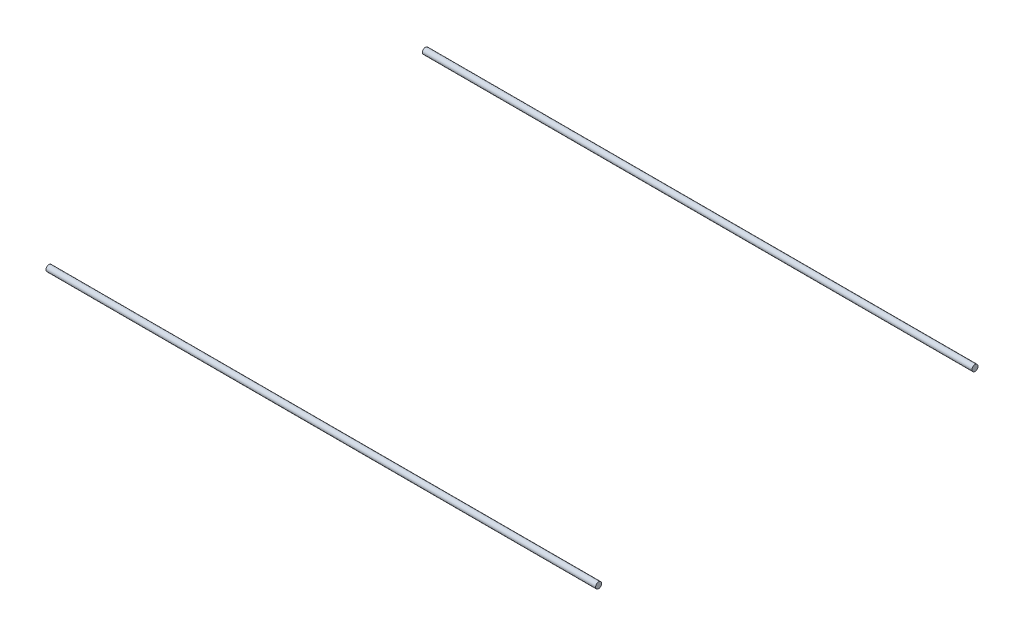
SolidWorks part; units mm, degrees
ref_plane "Front Plane" through (0, 0, 0) normal (0, 0, 1) x (1, 0, 0)
ref_plane "Top Plane" through (0, 0, 0) normal (0, 1, 0) x (1, 0, 0)
ref_plane "Right Plane" through (0, 0, 0) normal (1, 0, 0) x (0, 0, -1)
sketch "Sketch1" plane through (0, 0, 0) normal (0, 1, 0) x (1, 0, 0)
  line L1 (-350, 250) -> (350, 250)
  line L2 (-350, 250) -> (-350, -250)
  line L3 (-350, -250) -> (350, -250)
  line L4 (350, 250) -> (350, -250)
  line L5 (-350, 250) -> (350, -250) construction
  line L6 (-350, -250) -> (350, 250) construction
  point P0 (0, 0)
  dimension "D1" = 700
  dimension "D2" = 500
sketch "Sketch13" plane through (0, 0, 0) normal (0, 0, 1) x (1, 0, 0)
  line L0 (363.7, 12.7) -> (363.7, 10.5)
  line L1 (360.5, 9.5) -> (362.7, 9.5)
  line L2 (359.5, 12.7) -> (359.5, 10.5)
  line L3 (360.5, 13.7) -> (362.7, 13.7)
  line L4 (353.1359, 4.5184) -> (351.6001, 3.2806)
  line L5 (353.2806, 1.6001) -> (354.5053, 3.1547)
  line L6 (356.0045, 0.9) -> (355.4849, 0)
  line L7 (356.0045, 4.2045) -> (356.0045, 0.9)
  line L8 (350, -5.4849) -> (350.9, -6)
  line L9 (350.9, -6) -> (354.2045, -6)
  line L10 (354.2045, -6) -> (358.25, -10.05)
  line L11 (358.25, -10.05) -> (358.25, -12.6)
  line L12 (354.65, -12.8) -> (358.05, -12.8)
  line L13 (354.05, -14.3) -> (354.05, -13.4)
  line L14 (354.25, -14.5) -> (354.35, -14.5)
  line L15 (354.55, -14.8) -> (354.55, -14.7)
  line L16 (354.75, -15) -> (363, -15)
  line L17 (365, -13) -> (365, -4.75)
  line L18 (364.7, -4.55) -> (364.8, -4.55)
  line L19 (364.5, -4.35) -> (364.5, -4.25)
  line L20 (363.4, -4.05) -> (364.3, -4.05)
  line L21 (362.8, -8.05) -> (362.8, -4.65)
  line L22 (362.6, -8.25) -> (360.05, -8.25)
  line L23 (360.05, -8.25) -> (356.0045, -4.2045)
  line L24 (356.0045, -4.2045) -> (356.0045, -0.9)
  line L25 (356.0045, -0.9) -> (355.4849, 0)
  line L26 (360.05, 8.25) -> (356.0045, 4.2045)
  line L27 (362.6, 8.25) -> (360.05, 8.25)
  line L28 (362.8, 8.05) -> (362.8, 4.65)
  line L29 (363.4, 4.05) -> (364.3, 4.05)
  line L30 (364.5, 4.35) -> (364.5, 4.25)
  line L31 (364.7, 4.55) -> (364.8, 4.55)
  line L32 (365, 13) -> (365, 4.75)
  line L33 (354.75, 15) -> (363, 15)
  line L34 (354.55, 14.8) -> (354.55, 14.7)
  line L35 (354.25, 14.5) -> (354.35, 14.5)
  line L36 (354.05, 14.3) -> (354.05, 13.4)
  line L37 (354.65, 12.8) -> (358.05, 12.8)
  line L38 (358.25, 10.05) -> (358.25, 12.6)
  line L39 (354.2045, 6) -> (358.25, 10.05)
  line L40 (350.9, 6) -> (354.2045, 6)
  line L41 (350, 5.4849) -> (350.9, 6)
  line L42 (336.3, -12.7) -> (336.3, -10.5)
  line L43 (339.5, -9.5) -> (337.3, -9.5)
  line L44 (340.5, -12.7) -> (340.5, -10.5)
  line L45 (339.5, -13.7) -> (337.3, -13.7)
  line L46 (346.8641, -4.5184) -> (348.3999, -3.2806)
  line L47 (346.7194, -1.6001) -> (345.4947, -3.1547)
  line L48 (350, 5.4849) -> (349.1, 6)
  line L49 (349.1, 6) -> (345.7955, 6)
  line L50 (345.7955, 6) -> (341.75, 10.05)
  line L51 (341.75, 10.05) -> (341.75, 12.6)
  line L52 (345.35, 12.8) -> (341.95, 12.8)
  line L53 (345.95, 14.3) -> (345.95, 13.4)
  line L54 (345.75, 14.5) -> (345.65, 14.5)
  line L55 (345.45, 14.8) -> (345.45, 14.7)
  line L56 (345.25, 15) -> (337, 15)
  line L57 (335, 13) -> (335, 4.75)
  line L58 (335.3, 4.55) -> (335.2, 4.55)
  line L59 (335.5, 4.35) -> (335.5, 4.25)
  line L60 (336.6, 4.05) -> (335.7, 4.05)
  line L61 (337.2, 8.05) -> (337.2, 4.65)
  line L62 (337.4, 8.25) -> (339.95, 8.25)
  line L63 (339.95, 8.25) -> (343.9955, 4.2045)
  line L64 (343.9955, -0.9) -> (344.5151, 0)
  line L65 (343.9955, -4.2045) -> (343.9955, -0.9)
  line L66 (339.95, -8.25) -> (343.9955, -4.2045)
  line L67 (337.4, -8.25) -> (339.95, -8.25)
  line L68 (337.2, -8.05) -> (337.2, -4.65)
  line L69 (336.6, -4.05) -> (335.7, -4.05)
  line L70 (335.5, -4.35) -> (335.5, -4.25)
  line L71 (335.3, -4.55) -> (335.2, -4.55)
  line L72 (335, -13) -> (335, -4.75)
  line L73 (345.25, -15) -> (337, -15)
  line L74 (345.45, -14.8) -> (345.45, -14.7)
  line L75 (345.75, -14.5) -> (345.65, -14.5)
  line L76 (345.95, -14.3) -> (345.95, -13.4)
  line L77 (353.2806, -1.6001) -> (354.5053, -3.1547)
  line L78 (353.1359, -4.5184) -> (351.6001, -3.2806)
  line L79 (345.35, -12.8) -> (341.95, -12.8)
  line L80 (341.75, -10.05) -> (341.75, -12.6)
  line L81 (345.7955, -6) -> (341.75, -10.05)
  line L82 (349.1, -6) -> (345.7955, -6)
  line L83 (350, -5.4849) -> (349.1, -6)
  line L84 (360.5, -13.7) -> (362.7, -13.7)
  line L85 (359.5, -12.7) -> (359.5, -10.5)
  line L86 (360.5, -9.5) -> (362.7, -9.5)
  line L87 (363.7, -12.7) -> (363.7, -10.5)
  line L88 (343.9955, 4.2045) -> (343.9955, 0.9)
  line L89 (343.9955, 0.9) -> (344.5151, 0)
  line L90 (346.7194, 1.6001) -> (345.4947, 3.1547)
  line L91 (346.8641, 4.5184) -> (348.3999, 3.2806)
  line L92 (339.5, 13.7) -> (337.3, 13.7)
  line L93 (340.5, 12.7) -> (340.5, 10.5)
  line L94 (339.5, 9.5) -> (337.3, 9.5)
  line L95 (336.3, 12.7) -> (336.3, 10.5)
  line L96 (335, 0) -> (365, 0) construction
  line L97 (350, 15) -> (350, -15) construction
  line L98 (-337.4, 8.25) -> (-339.95, 8.25)
  line L99 (-354.2045, 6) -> (-358.25, 10.05)
  line L100 (-360.05, -8.25) -> (-356.0045, -4.2045)
  line L101 (-336.3, -12.7) -> (-336.3, -10.5)
  line L102 (-346.7194, 1.6001) -> (-345.4947, 3.1547)
  line L103 (-337.2, 8.05) -> (-337.2, 4.65)
  line L104 (-335.5, 4.35) -> (-335.5, 4.25)
  line L105 (-350, 5.4849) -> (-350.9, 6)
  line L106 (-362.8, 8.05) -> (-362.8, 4.65)
  line L107 (-350.9, -6) -> (-354.2045, -6)
  line L108 (-343.9955, 0.9) -> (-344.5151, 0)
  line L109 (-343.9955, 4.2045) -> (-343.9955, 0.9)
  line L110 (-339.95, -8.25) -> (-343.9955, -4.2045)
  line L111 (-345.75, 14.5) -> (-345.65, 14.5)
  line L112 (-354.05, 14.3) -> (-354.05, 13.4)
  line L113 (-350, -5.4849) -> (-350.9, -6)
  line L114 (-356.0045, 4.2045) -> (-356.0045, 0.9)
  line L115 (-336.3, 12.7) -> (-336.3, 10.5)
  line L116 (-349.1, -6) -> (-345.7955, -6)
  line L117 (-345.45, 14.8) -> (-345.45, 14.7)
  line L118 (-359.5, -12.7) -> (-359.5, -10.5)
  line L119 (-362.8, -8.05) -> (-362.8, -4.65)
  line L120 (-354.05, -14.3) -> (-354.05, -13.4)
  line L121 (-336.6, -4.05) -> (-335.7, -4.05)
  line L122 (-360.5, -9.5) -> (-362.7, -9.5)
  line L123 (-362.6, 8.25) -> (-360.05, 8.25)
  line L124 (-346.7194, -1.6001) -> (-345.4947, -3.1547)
  line L125 (-363.7, 12.7) -> (-363.7, 10.5)
  line L126 (-345.95, -14.3) -> (-345.95, -13.4)
  line L127 (-358.25, 10.05) -> (-358.25, 12.6)
  line L128 (-354.75, 15) -> (-363, 15)
  line L129 (-364.7, -4.55) -> (-364.8, -4.55)
  line L130 (-356.0045, 0.9) -> (-355.4849, 0)
  line L131 (-350, 15) -> (-350, -15) construction
  line L132 (-341.75, -10.05) -> (-341.75, -12.6)
  line L133 (-345.45, -14.8) -> (-345.45, -14.7)
  line L134 (-335.3, 4.55) -> (-335.2, 4.55)
  line L135 (-345.25, 15) -> (-337, 15)
  line L136 (-364.7, 4.55) -> (-364.8, 4.55)
  line L137 (-339.5, -13.7) -> (-337.3, -13.7)
  line L138 (-360.5, 9.5) -> (-362.7, 9.5)
  line L139 (-339.5, 9.5) -> (-337.3, 9.5)
  line L140 (-345.25, -15) -> (-337, -15)
  line L141 (-343.9955, -4.2045) -> (-343.9955, -0.9)
  line L142 (-341.75, 10.05) -> (-341.75, 12.6)
  line L143 (-354.25, 14.5) -> (-354.35, 14.5)
  line L144 (-360.05, 8.25) -> (-356.0045, 4.2045)
  line L145 (-346.8641, 4.5184) -> (-348.3999, 3.2806)
  line L146 (-345.35, -12.8) -> (-341.95, -12.8)
  line L147 (-345.95, 14.3) -> (-345.95, 13.4)
  line L148 (-360.5, -13.7) -> (-362.7, -13.7)
  line L149 (-364.5, -4.35) -> (-364.5, -4.25)
  line L150 (-346.8641, -4.5184) -> (-348.3999, -3.2806)
  line L151 (-337.4, -8.25) -> (-339.95, -8.25)
  line L152 (-353.1359, -4.5184) -> (-351.6001, -3.2806)
  line L153 (-362.6, -8.25) -> (-360.05, -8.25)
  line L154 (-354.65, -12.8) -> (-358.05, -12.8)
  line L155 (-353.1359, 4.5184) -> (-351.6001, 3.2806)
  line L156 (-345.7955, -6) -> (-341.75, -10.05)
  line L157 (-345.7955, 6) -> (-341.75, 10.05)
  line L158 (-354.65, 12.8) -> (-358.05, 12.8)
  line L159 (-354.55, 14.8) -> (-354.55, 14.7)
  line L160 (-365, -13) -> (-365, -4.75)
  line L161 (-353.2806, 1.6001) -> (-354.5053, 3.1547)
  line L162 (-365, 0) -> (-335, 0) construction
  line L163 (-345.75, -14.5) -> (-345.65, -14.5)
  line L164 (-335, -13) -> (-335, -4.75)
  line L165 (-345.35, 12.8) -> (-341.95, 12.8)
  line L166 (-364.5, 4.35) -> (-364.5, 4.25)
  line L167 (-354.75, -15) -> (-363, -15)
  line L168 (-340.5, -12.7) -> (-340.5, -10.5)
  line L169 (-335.3, -4.55) -> (-335.2, -4.55)
  line L170 (-343.9955, -0.9) -> (-344.5151, 0)
  line L171 (-350.9, 6) -> (-354.2045, 6)
  line L172 (-356.0045, -0.9) -> (-355.4849, 0)
  line L173 (-339.5, -9.5) -> (-337.3, -9.5)
  line L174 (-340.5, 12.7) -> (-340.5, 10.5)
  line L175 (-339.95, 8.25) -> (-343.9955, 4.2045)
  line L176 (-335, 13) -> (-335, 4.75)
  line L177 (-353.2806, -1.6001) -> (-354.5053, -3.1547)
  line L178 (-365, 13) -> (-365, 4.75)
  line L179 (-358.25, -10.05) -> (-358.25, -12.6)
  line L180 (-360.5, 13.7) -> (-362.7, 13.7)
  line L181 (-339.5, 13.7) -> (-337.3, 13.7)
  line L182 (-337.2, -8.05) -> (-337.2, -4.65)
  line L183 (-350, 5.4849) -> (-349.1, 6)
  line L184 (-363.4, -4.05) -> (-364.3, -4.05)
  line L185 (-354.2045, -6) -> (-358.25, -10.05)
  line L186 (-359.5, 12.7) -> (-359.5, 10.5)
  line L187 (-350, -5.4849) -> (-349.1, -6)
  line L188 (-336.6, 4.05) -> (-335.7, 4.05)
  line L189 (-349.1, 6) -> (-345.7955, 6)
  line L190 (-356.0045, -4.2045) -> (-356.0045, -0.9)
  line L191 (-354.55, -14.8) -> (-354.55, -14.7)
  line L192 (-335.5, -4.35) -> (-335.5, -4.25)
  line L193 (-363.7, -12.7) -> (-363.7, -10.5)
  line L194 (-363.4, 4.05) -> (-364.3, 4.05)
  line L195 (-354.25, -14.5) -> (-354.35, -14.5)
  arc A0 (363.7, 12.7) -> (362.7, 13.7) centre (362.7, 12.7) ccw
  arc A1 (362.7, 9.5) -> (363.7, 10.5) centre (362.7, 10.5) ccw
  arc A2 (359.5, 10.5) -> (360.5, 9.5) centre (360.5, 10.5) ccw
  arc A3 (360.5, 13.7) -> (359.5, 12.7) centre (360.5, 12.7) ccw
  arc A4 (351.6001, 3.2806) -> (348.3999, 3.2806) centre (350, 0) ccw
  arc A5 (358.25, -12.6) -> (358.05, -12.8) centre (358.05, -12.6) cw
  arc A6 (354.65, -12.8) -> (354.05, -13.4) centre (354.65, -13.4) ccw
  arc A7 (354.05, -14.3) -> (354.25, -14.5) centre (354.25, -14.3) ccw
  arc A8 (354.35, -14.5) -> (354.55, -14.7) centre (354.35, -14.7) cw
  arc A9 (354.55, -14.8) -> (354.75, -15) centre (354.75, -14.8) ccw
  arc A10 (363, -15) -> (365, -13) centre (363, -13) ccw
  arc A11 (365, -4.75) -> (364.8, -4.55) centre (364.8, -4.75) ccw
  arc A12 (364.7, -4.55) -> (364.5, -4.35) centre (364.7, -4.35) cw
  arc A13 (364.5, -4.25) -> (364.3, -4.05) centre (364.3, -4.25) ccw
  arc A14 (363.4, -4.05) -> (362.8, -4.65) centre (363.4, -4.65) ccw
  arc A15 (362.8, -8.05) -> (362.6, -8.25) centre (362.6, -8.05) cw
  arc A16 (354.5053, 3.1547) -> (353.1359, 4.5184) centre (350, 0) ccw
  arc A17 (362.8, 8.05) -> (362.6, 8.25) centre (362.6, 8.05) ccw
  arc A18 (363.4, 4.05) -> (362.8, 4.65) centre (363.4, 4.65) cw
  arc A19 (364.5, 4.25) -> (364.3, 4.05) centre (364.3, 4.25) cw
  arc A20 (364.7, 4.55) -> (364.5, 4.35) centre (364.7, 4.35) ccw
  arc A21 (365, 4.75) -> (364.8, 4.55) centre (364.8, 4.75) cw
  arc A22 (363, 15) -> (365, 13) centre (363, 13) cw
  arc A23 (354.55, 14.8) -> (354.75, 15) centre (354.75, 14.8) cw
  arc A24 (354.35, 14.5) -> (354.55, 14.7) centre (354.35, 14.7) ccw
  arc A25 (354.05, 14.3) -> (354.25, 14.5) centre (354.25, 14.3) cw
  arc A26 (354.65, 12.8) -> (354.05, 13.4) centre (354.65, 13.4) cw
  arc A27 (358.25, 12.6) -> (358.05, 12.8) centre (358.05, 12.6) ccw
  arc A28 (336.3, -12.7) -> (337.3, -13.7) centre (337.3, -12.7) ccw
  arc A29 (337.3, -9.5) -> (336.3, -10.5) centre (337.3, -10.5) ccw
  arc A30 (340.5, -10.5) -> (339.5, -9.5) centre (339.5, -10.5) ccw
  arc A31 (339.5, -13.7) -> (340.5, -12.7) centre (339.5, -12.7) ccw
  arc A32 (345.4947, -3.1547) -> (346.8641, -4.5184) centre (350, 0) ccw
  arc A33 (346.7194, 1.6001) -> (346.7194, -1.6001) centre (350, 0) ccw
  arc A34 (341.75, 12.6) -> (341.95, 12.8) centre (341.95, 12.6) cw
  arc A35 (345.35, 12.8) -> (345.95, 13.4) centre (345.35, 13.4) ccw
  arc A36 (345.95, 14.3) -> (345.75, 14.5) centre (345.75, 14.3) ccw
  arc A37 (345.65, 14.5) -> (345.45, 14.7) centre (345.65, 14.7) cw
  arc A38 (345.45, 14.8) -> (345.25, 15) centre (345.25, 14.8) ccw
  arc A39 (337, 15) -> (335, 13) centre (337, 13) ccw
  arc A40 (335, 4.75) -> (335.2, 4.55) centre (335.2, 4.75) ccw
  arc A41 (335.3, 4.55) -> (335.5, 4.35) centre (335.3, 4.35) cw
  arc A42 (335.5, 4.25) -> (335.7, 4.05) centre (335.7, 4.25) ccw
  arc A43 (336.6, 4.05) -> (337.2, 4.65) centre (336.6, 4.65) ccw
  arc A44 (337.2, 8.05) -> (337.4, 8.25) centre (337.4, 8.05) cw
  arc A45 (345.4947, 3.1547) -> (346.8641, 4.5184) centre (350, 0) cw
  arc A46 (337.2, -8.05) -> (337.4, -8.25) centre (337.4, -8.05) ccw
  arc A47 (336.6, -4.05) -> (337.2, -4.65) centre (336.6, -4.65) cw
  arc A48 (335.5, -4.25) -> (335.7, -4.05) centre (335.7, -4.25) cw
  arc A49 (353.2806, 1.6001) -> (353.2806, -1.6001) centre (350, 0) cw
  arc A50 (354.5053, -3.1547) -> (353.1359, -4.5184) centre (350, 0) cw
  arc A51 (351.6001, -3.2806) -> (348.3999, -3.2806) centre (350, 0) cw
  arc A52 (335.3, -4.55) -> (335.5, -4.35) centre (335.3, -4.35) ccw
  arc A53 (335, -4.75) -> (335.2, -4.55) centre (335.2, -4.75) cw
  arc A54 (337, -15) -> (335, -13) centre (337, -13) cw
  arc A55 (345.45, -14.8) -> (345.25, -15) centre (345.25, -14.8) cw
  arc A56 (360.5, -13.7) -> (359.5, -12.7) centre (360.5, -12.7) cw
  arc A57 (359.5, -10.5) -> (360.5, -9.5) centre (360.5, -10.5) cw
  arc A58 (362.7, -9.5) -> (363.7, -10.5) centre (362.7, -10.5) cw
  arc A59 (363.7, -12.7) -> (362.7, -13.7) centre (362.7, -12.7) cw
  arc A60 (345.65, -14.5) -> (345.45, -14.7) centre (345.65, -14.7) ccw
  arc A61 (345.95, -14.3) -> (345.75, -14.5) centre (345.75, -14.3) cw
  arc A62 (345.35, -12.8) -> (345.95, -13.4) centre (345.35, -13.4) cw
  arc A63 (341.75, -12.6) -> (341.95, -12.8) centre (341.95, -12.6) ccw
  arc A64 (339.5, 13.7) -> (340.5, 12.7) centre (339.5, 12.7) cw
  arc A65 (340.5, 10.5) -> (339.5, 9.5) centre (339.5, 10.5) cw
  arc A66 (337.3, 9.5) -> (336.3, 10.5) centre (337.3, 10.5) cw
  arc A67 (336.3, 12.7) -> (337.3, 13.7) centre (337.3, 12.7) cw
  arc A68 (-335.5, -4.25) -> (-335.7, -4.05) centre (-335.7, -4.25) ccw
  arc A69 (-335, 4.75) -> (-335.2, 4.55) centre (-335.2, 4.75) cw
  arc A70 (-360.5, -13.7) -> (-359.5, -12.7) centre (-360.5, -12.7) ccw
  arc A71 (-354.65, -12.8) -> (-354.05, -13.4) centre (-354.65, -13.4) cw
  arc A72 (-360.5, 13.7) -> (-359.5, 12.7) centre (-360.5, 12.7) cw
  arc A73 (-340.5, 10.5) -> (-339.5, 9.5) centre (-339.5, 10.5) ccw
  arc A74 (-337, 15) -> (-335, 13) centre (-337, 13) cw
  arc A75 (-345.95, 14.3) -> (-345.75, 14.5) centre (-345.75, 14.3) cw
  arc A76 (-345.35, 12.8) -> (-345.95, 13.4) centre (-345.35, 13.4) cw
  arc A77 (-339.5, -13.7) -> (-340.5, -12.7) centre (-339.5, -12.7) cw
  arc A78 (-362.7, 9.5) -> (-363.7, 10.5) centre (-362.7, 10.5) cw
  arc A79 (-345.65, -14.5) -> (-345.45, -14.7) centre (-345.65, -14.7) cw
  arc A80 (-354.5053, 3.1547) -> (-353.1359, 4.5184) centre (-350, 0) cw
  arc A81 (-363, -15) -> (-365, -13) centre (-363, -13) cw
  arc A82 (-341.75, -12.6) -> (-341.95, -12.8) centre (-341.95, -12.6) cw
  arc A83 (-345.35, -12.8) -> (-345.95, -13.4) centre (-345.35, -13.4) ccw
  arc A84 (-354.35, 14.5) -> (-354.55, 14.7) centre (-354.35, 14.7) cw
  arc A85 (-363, 15) -> (-365, 13) centre (-363, 13) ccw
  arc A86 (-358.25, -12.6) -> (-358.05, -12.8) centre (-358.05, -12.6) ccw
  arc A87 (-337.3, 9.5) -> (-336.3, 10.5) centre (-337.3, 10.5) ccw
  arc A88 (-341.75, 12.6) -> (-341.95, 12.8) centre (-341.95, 12.6) ccw
  arc A89 (-364.5, 4.25) -> (-364.3, 4.05) centre (-364.3, 4.25) ccw
  arc A90 (-359.5, 10.5) -> (-360.5, 9.5) centre (-360.5, 10.5) cw
  arc A91 (-363.4, 4.05) -> (-362.8, 4.65) centre (-363.4, 4.65) ccw
  arc A92 (-362.8, 8.05) -> (-362.6, 8.25) centre (-362.6, 8.05) cw
  arc A93 (-363.7, 12.7) -> (-362.7, 13.7) centre (-362.7, 12.7) cw
  arc A94 (-335.3, -4.55) -> (-335.5, -4.35) centre (-335.3, -4.35) cw
  arc A95 (-359.5, -10.5) -> (-360.5, -9.5) centre (-360.5, -10.5) ccw
  arc A96 (-364.7, -4.55) -> (-364.5, -4.35) centre (-364.7, -4.35) ccw
  arc A97 (-337.3, -9.5) -> (-336.3, -10.5) centre (-337.3, -10.5) cw
  arc A98 (-345.45, -14.8) -> (-345.25, -15) centre (-345.25, -14.8) ccw
  arc A99 (-337, -15) -> (-335, -13) centre (-337, -13) ccw
  arc A100 (-362.8, -8.05) -> (-362.6, -8.25) centre (-362.6, -8.05) ccw
  arc A101 (-345.4947, -3.1547) -> (-346.8641, -4.5184) centre (-350, 0) cw
  arc A102 (-337.2, -8.05) -> (-337.4, -8.25) centre (-337.4, -8.05) cw
  arc A103 (-336.6, 4.05) -> (-337.2, 4.65) centre (-336.6, 4.65) cw
  arc A104 (-345.45, 14.8) -> (-345.25, 15) centre (-345.25, 14.8) cw
  arc A105 (-363.4, -4.05) -> (-362.8, -4.65) centre (-363.4, -4.65) cw
  arc A106 (-339.5, 13.7) -> (-340.5, 12.7) centre (-339.5, 12.7) ccw
  arc A107 (-354.5053, -3.1547) -> (-353.1359, -4.5184) centre (-350, 0) ccw
  arc A108 (-364.5, -4.25) -> (-364.3, -4.05) centre (-364.3, -4.25) cw
  arc A109 (-354.35, -14.5) -> (-354.55, -14.7) centre (-354.35, -14.7) ccw
  arc A110 (-363.7, -12.7) -> (-362.7, -13.7) centre (-362.7, -12.7) ccw
  arc A111 (-346.7194, 1.6001) -> (-346.7194, -1.6001) centre (-350, 0) cw
  arc A112 (-336.3, 12.7) -> (-337.3, 13.7) centre (-337.3, 12.7) ccw
  arc A113 (-345.95, -14.3) -> (-345.75, -14.5) centre (-345.75, -14.3) ccw
  arc A114 (-358.25, 12.6) -> (-358.05, 12.8) centre (-358.05, 12.6) cw
  arc A115 (-354.55, 14.8) -> (-354.75, 15) centre (-354.75, 14.8) ccw
  arc A116 (-354.05, -14.3) -> (-354.25, -14.5) centre (-354.25, -14.3) cw
  arc A117 (-337.2, 8.05) -> (-337.4, 8.25) centre (-337.4, 8.05) ccw
  arc A118 (-335.3, 4.55) -> (-335.5, 4.35) centre (-335.3, 4.35) ccw
  arc A119 (-354.65, 12.8) -> (-354.05, 13.4) centre (-354.65, 13.4) ccw
  arc A120 (-354.55, -14.8) -> (-354.75, -15) centre (-354.75, -14.8) cw
  arc A121 (-340.5, -10.5) -> (-339.5, -9.5) centre (-339.5, -10.5) cw
  arc A122 (-335.5, 4.25) -> (-335.7, 4.05) centre (-335.7, 4.25) cw
  arc A123 (-362.7, -9.5) -> (-363.7, -10.5) centre (-362.7, -10.5) ccw
  arc A124 (-348.3999, -3.2806) -> (-351.6001, -3.2806) centre (-350, 0) cw
  arc A125 (-348.3999, 3.2806) -> (-351.6001, 3.2806) centre (-350, 0) ccw
  arc A126 (-365, 4.75) -> (-364.8, 4.55) centre (-364.8, 4.75) ccw
  arc A127 (-365, -4.75) -> (-364.8, -4.55) centre (-364.8, -4.75) cw
  arc A128 (-336.6, -4.05) -> (-337.2, -4.65) centre (-336.6, -4.65) ccw
  arc A129 (-345.65, 14.5) -> (-345.45, 14.7) centre (-345.65, 14.7) ccw
  arc A130 (-353.2806, 1.6001) -> (-353.2806, -1.6001) centre (-350, 0) ccw
  arc A131 (-335, -4.75) -> (-335.2, -4.55) centre (-335.2, -4.75) ccw
  arc A132 (-345.4947, 3.1547) -> (-346.8641, 4.5184) centre (-350, 0) ccw
  arc A133 (-354.05, 14.3) -> (-354.25, 14.5) centre (-354.25, 14.3) ccw
  arc A134 (-364.7, 4.55) -> (-364.5, 4.35) centre (-364.7, 4.35) cw
  arc A135 (-336.3, -12.7) -> (-337.3, -13.7) centre (-337.3, -12.7) cw
  point P81 (365, 15)
  point P82 (350, 15)
  point P203 (350, -15)
  point P204 (365, -15)
  point P206 (350, 0)
  point P207 (365, 0)
  point P219 (335, 0)
  point P220 (335, -15)
  point P221 (335, 15)
  point P319 (-335, 15)
  point P320 (-350, 15)
  point P441 (-350, -15)
  point P442 (-335, -15)
  point P444 (-350, 0)
  point P445 (-335, 0)
  point P457 (-365, 0)
  point P458 (-365, -15)
  point P459 (-365, 15)
extrude "Boss-Extrude1" add sketch "Sketch13" along normal mid plane 530
sketch "Sketch14" plane through (0, 0, 0) normal (1, 0, 0) x (0, 0, -1)
  line L194 (-246.8641, 4.5184) -> (-248.3999, 3.2806)
  line L195 (-235.3, 4.55) -> (-235.2, 4.55)
  line L196 (-260.5, -9.5) -> (-262.7, -9.5)
  line L197 (-258.25, 10.05) -> (-258.25, 12.6)
  line L198 (-264.5, -4.35) -> (-264.5, -4.25)
  line L199 (-259.5, 12.7) -> (-259.5, 10.5)
  line L200 (-250, -5.4849) -> (-249.1, -6)
  line L201 (-237.4, -8.25) -> (-239.95, -8.25)
  line L202 (-254.55, 14.8) -> (-254.55, 14.7)
  line L203 (-262.8, 8.05) -> (-262.8, 4.65)
  line L204 (-262.6, -8.25) -> (-260.05, -8.25)
  line L205 (-250, 15) -> (-250, -15) construction
  line L206 (-236.3, 12.7) -> (-236.3, 10.5)
  line L207 (-239.95, 8.25) -> (-243.9955, 4.2045)
  line L208 (-241.75, 10.05) -> (-241.75, 12.6)
  line L209 (-253.1359, -4.5184) -> (-251.6001, -3.2806)
  line L210 (-254.25, -14.5) -> (-254.35, -14.5)
  line L211 (-256.0045, 0.9) -> (-255.4849, 0)
  line L212 (-243.9955, -4.2045) -> (-243.9955, -0.9)
  line L213 (-245.7955, 6) -> (-241.75, 10.05)
  line L214 (-253.2806, -1.6001) -> (-254.5053, -3.1547)
  line L215 (-254.55, -14.8) -> (-254.55, -14.7)
  line L216 (-250.9, -6) -> (-254.2045, -6)
  line L217 (-245.35, -12.8) -> (-241.95, -12.8)
  line L218 (-243.9955, -0.9) -> (-244.5151, 0)
  line L219 (-249.1, 6) -> (-245.7955, 6)
  line L220 (-254.05, -14.3) -> (-254.05, -13.4)
  line L221 (-250, -5.4849) -> (-250.9, -6)
  line L222 (-265, 0) -> (-235, 0) construction
  line L223 (-243.9955, 0.9) -> (-244.5151, 0)
  line L224 (-245.75, -14.5) -> (-245.65, -14.5)
  line L225 (-235.5, -4.35) -> (-235.5, -4.25)
  line L226 (-263.7, -12.7) -> (-263.7, -10.5)
  line L227 (-250.9, 6) -> (-254.2045, 6)
  line L228 (-246.8641, -4.5184) -> (-248.3999, -3.2806)
  line L229 (-260.5, 9.5) -> (-262.7, 9.5)
  line L230 (-245.45, -14.8) -> (-245.45, -14.7)
  line L231 (-235.5, 4.35) -> (-235.5, 4.25)
  line L232 (-260.5, -13.7) -> (-262.7, -13.7)
  line L233 (-254.2045, 6) -> (-258.25, 10.05)
  line L234 (-265, -13) -> (-265, -4.75)
  line L235 (-239.95, -8.25) -> (-243.9955, -4.2045)
  line L236 (-259.5, -12.7) -> (-259.5, -10.5)
  line L237 (-262.6, 8.25) -> (-260.05, 8.25)
  line L238 (-246.7194, -1.6001) -> (-245.4947, -3.1547)
  line L239 (-253.2806, 1.6001) -> (-254.5053, 3.1547)
  line L240 (-245.95, -14.3) -> (-245.95, -13.4)
  line L241 (-237.4, 8.25) -> (-239.95, 8.25)
  line L242 (-254.65, 12.8) -> (-258.05, 12.8)
  line L243 (-264.7, 4.55) -> (-264.8, 4.55)
  line L244 (-254.65, -12.8) -> (-258.05, -12.8)
  line L245 (-239.5, -9.5) -> (-237.3, -9.5)
  line L246 (-243.9955, 4.2045) -> (-243.9955, 0.9)
  line L247 (-235, -13) -> (-235, -4.75)
  line L248 (-236.6, -4.05) -> (-235.7, -4.05)
  line L249 (-250, 5.4849) -> (-249.1, 6)
  line L250 (-239.5, -13.7) -> (-237.3, -13.7)
  line L251 (-240.5, -12.7) -> (-240.5, -10.5)
  line L252 (-245.7955, -6) -> (-241.75, -10.05)
  line L253 (-237.2, 8.05) -> (-237.2, 4.65)
  line L254 (-254.25, 14.5) -> (-254.35, 14.5)
  line L255 (-260.05, -8.25) -> (-256.0045, -4.2045)
  line L256 (-258.25, -10.05) -> (-258.25, -12.6)
  line L257 (-236.3, -12.7) -> (-236.3, -10.5)
  line L258 (-240.5, 12.7) -> (-240.5, 10.5)
  line L259 (-235, 13) -> (-235, 4.75)
  line L260 (-263.4, 4.05) -> (-264.3, 4.05)
  line L261 (-260.05, 8.25) -> (-256.0045, 4.2045)
  line L262 (-254.75, -15) -> (-263, -15)
  line L263 (-239.5, 9.5) -> (-237.3, 9.5)
  line L264 (-235.3, -4.55) -> (-235.2, -4.55)
  line L265 (-250, 5.4849) -> (-250.9, 6)
  line L266 (-256.0045, -0.9) -> (-255.4849, 0)
  line L267 (-263.4, -4.05) -> (-264.3, -4.05)
  line L268 (-253.1359, 4.5184) -> (-251.6001, 3.2806)
  line L269 (-237.2, -8.05) -> (-237.2, -4.65)
  line L270 (-254.05, 14.3) -> (-254.05, 13.4)
  line L271 (-264.5, 4.35) -> (-264.5, 4.25)
  line L272 (-260.5, 13.7) -> (-262.7, 13.7)
  line L273 (-239.5, 13.7) -> (-237.3, 13.7)
  line L274 (-249.1, -6) -> (-245.7955, -6)
  line L275 (-236.6, 4.05) -> (-235.7, 4.05)
  line L276 (-245.35, 12.8) -> (-241.95, 12.8)
  line L277 (-254.75, 15) -> (-263, 15)
  line L278 (-254.2045, -6) -> (-258.25, -10.05)
  line L279 (-256.0045, 4.2045) -> (-256.0045, 0.9)
  line L280 (-246.7194, 1.6001) -> (-245.4947, 3.1547)
  line L281 (-245.25, -15) -> (-237, -15)
  line L282 (-245.25, 15) -> (-237, 15)
  line L283 (-245.75, 14.5) -> (-245.65, 14.5)
  line L284 (-265, 13) -> (-265, 4.75)
  line L285 (-264.7, -4.55) -> (-264.8, -4.55)
  line L286 (-263.7, 12.7) -> (-263.7, 10.5)
  line L287 (-241.75, -10.05) -> (-241.75, -12.6)
  line L288 (-245.45, 14.8) -> (-245.45, 14.7)
  line L289 (-245.95, 14.3) -> (-245.95, 13.4)
  line L290 (-256.0045, -4.2045) -> (-256.0045, -0.9)
  line L291 (-262.8, -8.05) -> (-262.8, -4.65)
  line L292 (253.1359, 4.5184) -> (251.6001, 3.2806)
  line L293 (264.7, 4.55) -> (264.8, 4.55)
  line L294 (239.5, -9.5) -> (237.3, -9.5)
  line L295 (241.75, 10.05) -> (241.75, 12.6)
  line L296 (235.5, -4.35) -> (235.5, -4.25)
  line L297 (240.5, 12.7) -> (240.5, 10.5)
  line L298 (250, -5.4849) -> (250.9, -6)
  line L299 (262.6, -8.25) -> (260.05, -8.25)
  line L300 (245.45, 14.8) -> (245.45, 14.7)
  line L301 (237.2, 8.05) -> (237.2, 4.65)
  line L302 (237.4, -8.25) -> (239.95, -8.25)
  line L303 (250, 15) -> (250, -15) construction
  line L304 (263.7, 12.7) -> (263.7, 10.5)
  line L305 (260.05, 8.25) -> (256.0045, 4.2045)
  line L306 (258.25, 10.05) -> (258.25, 12.6)
  line L307 (246.8641, -4.5184) -> (248.3999, -3.2806)
  line L308 (245.75, -14.5) -> (245.65, -14.5)
  line L309 (243.9955, 0.9) -> (244.5151, 0)
  line L310 (256.0045, -4.2045) -> (256.0045, -0.9)
  line L311 (254.2045, 6) -> (258.25, 10.05)
  line L312 (246.7194, -1.6001) -> (245.4947, -3.1547)
  line L313 (245.45, -14.8) -> (245.45, -14.7)
  line L314 (249.1, -6) -> (245.7955, -6)
  line L315 (254.65, -12.8) -> (258.05, -12.8)
  line L316 (256.0045, -0.9) -> (255.4849, 0)
  line L317 (250.9, 6) -> (254.2045, 6)
  line L318 (245.95, -14.3) -> (245.95, -13.4)
  line L319 (250, -5.4849) -> (249.1, -6)
  line L320 (235, 0) -> (265, 0) construction
  line L321 (256.0045, 0.9) -> (255.4849, 0)
  line L322 (254.25, -14.5) -> (254.35, -14.5)
  line L323 (264.5, -4.35) -> (264.5, -4.25)
  line L324 (236.3, -12.7) -> (236.3, -10.5)
  line L325 (249.1, 6) -> (245.7955, 6)
  line L326 (253.1359, -4.5184) -> (251.6001, -3.2806)
  line L327 (239.5, 9.5) -> (237.3, 9.5)
  line L328 (254.55, -14.8) -> (254.55, -14.7)
  line L329 (264.5, 4.35) -> (264.5, 4.25)
  line L330 (239.5, -13.7) -> (237.3, -13.7)
  line L331 (245.7955, 6) -> (241.75, 10.05)
  line L332 (235, -13) -> (235, -4.75)
  line L333 (260.05, -8.25) -> (256.0045, -4.2045)
  line L334 (240.5, -12.7) -> (240.5, -10.5)
  line L335 (237.4, 8.25) -> (239.95, 8.25)
  line L336 (253.2806, -1.6001) -> (254.5053, -3.1547)
  line L337 (246.7194, 1.6001) -> (245.4947, 3.1547)
  line L338 (254.05, -14.3) -> (254.05, -13.4)
  line L339 (262.6, 8.25) -> (260.05, 8.25)
  line L340 (245.35, 12.8) -> (241.95, 12.8)
  line L341 (235.3, 4.55) -> (235.2, 4.55)
  line L342 (245.35, -12.8) -> (241.95, -12.8)
  line L343 (260.5, -9.5) -> (262.7, -9.5)
  line L344 (256.0045, 4.2045) -> (256.0045, 0.9)
  line L345 (265, -13) -> (265, -4.75)
  line L346 (263.4, -4.05) -> (264.3, -4.05)
  line L347 (250, 5.4849) -> (250.9, 6)
  line L348 (260.5, -13.7) -> (262.7, -13.7)
  line L349 (259.5, -12.7) -> (259.5, -10.5)
  line L350 (254.2045, -6) -> (258.25, -10.05)
  line L351 (262.8, 8.05) -> (262.8, 4.65)
  line L352 (245.75, 14.5) -> (245.65, 14.5)
  line L353 (239.95, -8.25) -> (243.9955, -4.2045)
  line L354 (241.75, -10.05) -> (241.75, -12.6)
  line L355 (263.7, -12.7) -> (263.7, -10.5)
  line L356 (259.5, 12.7) -> (259.5, 10.5)
  line L357 (265, 13) -> (265, 4.75)
  line L358 (236.6, 4.05) -> (235.7, 4.05)
  line L359 (239.95, 8.25) -> (243.9955, 4.2045)
  line L360 (245.25, -15) -> (237, -15)
  line L361 (260.5, 9.5) -> (262.7, 9.5)
  line L362 (264.7, -4.55) -> (264.8, -4.55)
  line L363 (250, 5.4849) -> (249.1, 6)
  line L364 (243.9955, -0.9) -> (244.5151, 0)
  line L365 (236.6, -4.05) -> (235.7, -4.05)
  line L366 (246.8641, 4.5184) -> (248.3999, 3.2806)
  line L367 (262.8, -8.05) -> (262.8, -4.65)
  line L368 (245.95, 14.3) -> (245.95, 13.4)
  line L369 (235.5, 4.35) -> (235.5, 4.25)
  line L370 (239.5, 13.7) -> (237.3, 13.7)
  line L371 (260.5, 13.7) -> (262.7, 13.7)
  line L372 (250.9, -6) -> (254.2045, -6)
  line L373 (263.4, 4.05) -> (264.3, 4.05)
  line L374 (254.65, 12.8) -> (258.05, 12.8)
  line L375 (245.25, 15) -> (237, 15)
  line L376 (245.7955, -6) -> (241.75, -10.05)
  line L377 (243.9955, 4.2045) -> (243.9955, 0.9)
  line L378 (253.2806, 1.6001) -> (254.5053, 3.1547)
  line L379 (254.75, -15) -> (263, -15)
  line L380 (254.75, 15) -> (263, 15)
  line L381 (254.25, 14.5) -> (254.35, 14.5)
  line L382 (235, 13) -> (235, 4.75)
  line L383 (235.3, -4.55) -> (235.2, -4.55)
  line L384 (236.3, 12.7) -> (236.3, 10.5)
  line L385 (258.25, -10.05) -> (258.25, -12.6)
  line L386 (254.55, 14.8) -> (254.55, 14.7)
  line L387 (254.05, 14.3) -> (254.05, 13.4)
  line L388 (243.9955, -4.2045) -> (243.9955, -0.9)
  line L389 (237.2, -8.05) -> (237.2, -4.65)
  arc A136 (-236.6, 4.05) -> (-237.2, 4.65) centre (-236.6, 4.65) cw
  arc A137 (-245.35, 12.8) -> (-245.95, 13.4) centre (-245.35, 13.4) cw
  arc A138 (-254.5053, -3.1547) -> (-253.1359, -4.5184) centre (-250, 0) ccw
  arc A139 (-254.65, -12.8) -> (-254.05, -13.4) centre (-254.65, -13.4) cw
  arc A140 (-237.3, 9.5) -> (-236.3, 10.5) centre (-237.3, 10.5) ccw
  arc A141 (-245.35, -12.8) -> (-245.95, -13.4) centre (-245.35, -13.4) ccw
  arc A142 (-263.4, 4.05) -> (-262.8, 4.65) centre (-263.4, 4.65) ccw
  arc A143 (-263.4, -4.05) -> (-262.8, -4.65) centre (-263.4, -4.65) cw
  arc A144 (-263.7, -12.7) -> (-262.7, -13.7) centre (-262.7, -12.7) ccw
  arc A145 (-264.7, -4.55) -> (-264.5, -4.35) centre (-264.7, -4.35) ccw
  arc A146 (-259.5, 10.5) -> (-260.5, 9.5) centre (-260.5, 10.5) cw
  arc A147 (-235.3, -4.55) -> (-235.5, -4.35) centre (-235.3, -4.35) cw
  arc A148 (-237, 15) -> (-235, 13) centre (-237, 13) cw
  arc A149 (-263, 15) -> (-265, 13) centre (-263, 13) ccw
  arc A150 (-263.7, 12.7) -> (-262.7, 13.7) centre (-262.7, 12.7) cw
  arc A151 (-237.2, 8.05) -> (-237.4, 8.25) centre (-237.4, 8.05) ccw
  arc A152 (-235.5, 4.25) -> (-235.7, 4.05) centre (-235.7, 4.25) cw
  arc A153 (-246.7194, 1.6001) -> (-246.7194, -1.6001) centre (-250, 0) cw
  arc A154 (-254.05, -14.3) -> (-254.25, -14.5) centre (-254.25, -14.3) cw
  arc A155 (-245.65, -14.5) -> (-245.45, -14.7) centre (-245.65, -14.7) cw
  arc A156 (-258.25, 12.6) -> (-258.05, 12.8) centre (-258.05, 12.6) cw
  arc A157 (-254.65, 12.8) -> (-254.05, 13.4) centre (-254.65, 13.4) ccw
  arc A158 (-239.5, -13.7) -> (-240.5, -12.7) centre (-239.5, -12.7) cw
  arc A159 (-262.7, 9.5) -> (-263.7, 10.5) centre (-262.7, 10.5) cw
  arc A160 (-240.5, 10.5) -> (-239.5, 9.5) centre (-239.5, 10.5) ccw
  arc A161 (-237.2, -8.05) -> (-237.4, -8.25) centre (-237.4, -8.05) cw
  arc A162 (-262.7, -9.5) -> (-263.7, -10.5) centre (-262.7, -10.5) ccw
  arc A163 (-254.5053, 3.1547) -> (-253.1359, 4.5184) centre (-250, 0) cw
  arc A164 (-239.5, 13.7) -> (-240.5, 12.7) centre (-239.5, 12.7) ccw
  arc A165 (-245.65, 14.5) -> (-245.45, 14.7) centre (-245.65, 14.7) ccw
  arc A166 (-254.35, 14.5) -> (-254.55, 14.7) centre (-254.35, 14.7) cw
  arc A167 (-254.55, -14.8) -> (-254.75, -15) centre (-254.75, -14.8) cw
  arc A168 (-248.3999, 3.2806) -> (-251.6001, 3.2806) centre (-250, 0) ccw
  arc A169 (-260.5, -13.7) -> (-259.5, -12.7) centre (-260.5, -12.7) ccw
  arc A170 (-264.5, 4.25) -> (-264.3, 4.05) centre (-264.3, 4.25) ccw
  arc A171 (-237.3, -9.5) -> (-236.3, -10.5) centre (-237.3, -10.5) cw
  arc A172 (-235.3, 4.55) -> (-235.5, 4.35) centre (-235.3, 4.35) ccw
  arc A173 (-245.4947, -3.1547) -> (-246.8641, -4.5184) centre (-250, 0) cw
  arc A174 (-260.5, 13.7) -> (-259.5, 12.7) centre (-260.5, 12.7) cw
  arc A175 (-245.45, -14.8) -> (-245.25, -15) centre (-245.25, -14.8) ccw
  arc A176 (-235, 4.75) -> (-235.2, 4.55) centre (-235.2, 4.75) cw
  arc A177 (-253.2806, 1.6001) -> (-253.2806, -1.6001) centre (-250, 0) ccw
  arc A178 (-265, -4.75) -> (-264.8, -4.55) centre (-264.8, -4.75) cw
  arc A179 (-236.3, -12.7) -> (-237.3, -13.7) centre (-237.3, -12.7) cw
  arc A180 (-237, -15) -> (-235, -13) centre (-237, -13) ccw
  arc A181 (-262.8, 8.05) -> (-262.6, 8.25) centre (-262.6, 8.05) cw
  arc A182 (-262.8, -8.05) -> (-262.6, -8.25) centre (-262.6, -8.05) ccw
  arc A183 (-245.95, 14.3) -> (-245.75, 14.5) centre (-245.75, 14.3) cw
  arc A184 (-259.5, -10.5) -> (-260.5, -9.5) centre (-260.5, -10.5) ccw
  arc A185 (-240.5, -10.5) -> (-239.5, -9.5) centre (-239.5, -10.5) cw
  arc A186 (-236.3, 12.7) -> (-237.3, 13.7) centre (-237.3, 12.7) ccw
  arc A187 (-241.75, -12.6) -> (-241.95, -12.8) centre (-241.95, -12.6) cw
  arc A188 (-236.6, -4.05) -> (-237.2, -4.65) centre (-236.6, -4.65) ccw
  arc A189 (-241.75, 12.6) -> (-241.95, 12.8) centre (-241.95, 12.6) ccw
  arc A190 (-265, 4.75) -> (-264.8, 4.55) centre (-264.8, 4.75) ccw
  arc A191 (-245.95, -14.3) -> (-245.75, -14.5) centre (-245.75, -14.3) ccw
  arc A192 (-245.45, 14.8) -> (-245.25, 15) centre (-245.25, 14.8) cw
  arc A193 (-254.05, 14.3) -> (-254.25, 14.5) centre (-254.25, 14.3) ccw
  arc A194 (-258.25, -12.6) -> (-258.05, -12.8) centre (-258.05, -12.6) ccw
  arc A195 (-235, -4.75) -> (-235.2, -4.55) centre (-235.2, -4.75) ccw
  arc A196 (-254.55, 14.8) -> (-254.75, 15) centre (-254.75, 14.8) ccw
  arc A197 (-264.7, 4.55) -> (-264.5, 4.35) centre (-264.7, 4.35) cw
  arc A198 (-263, -15) -> (-265, -13) centre (-263, -13) cw
  arc A199 (-235.5, -4.25) -> (-235.7, -4.05) centre (-235.7, -4.25) ccw
  arc A200 (-245.4947, 3.1547) -> (-246.8641, 4.5184) centre (-250, 0) ccw
  arc A201 (-264.5, -4.25) -> (-264.3, -4.05) centre (-264.3, -4.25) cw
  arc A202 (-248.3999, -3.2806) -> (-251.6001, -3.2806) centre (-250, 0) cw
  arc A203 (-254.35, -14.5) -> (-254.55, -14.7) centre (-254.35, -14.7) ccw
  arc A204 (263.4, 4.05) -> (262.8, 4.65) centre (263.4, 4.65) cw
  arc A205 (254.65, 12.8) -> (254.05, 13.4) centre (254.65, 13.4) cw
  arc A206 (245.4947, -3.1547) -> (246.8641, -4.5184) centre (250, 0) ccw
  arc A207 (245.35, -12.8) -> (245.95, -13.4) centre (245.35, -13.4) cw
  arc A208 (262.7, 9.5) -> (263.7, 10.5) centre (262.7, 10.5) ccw
  arc A209 (254.65, -12.8) -> (254.05, -13.4) centre (254.65, -13.4) ccw
  arc A210 (236.6, 4.05) -> (237.2, 4.65) centre (236.6, 4.65) ccw
  arc A211 (236.6, -4.05) -> (237.2, -4.65) centre (236.6, -4.65) cw
  arc A212 (236.3, -12.7) -> (237.3, -13.7) centre (237.3, -12.7) ccw
  arc A213 (235.3, -4.55) -> (235.5, -4.35) centre (235.3, -4.35) ccw
  arc A214 (240.5, 10.5) -> (239.5, 9.5) centre (239.5, 10.5) cw
  arc A215 (264.7, -4.55) -> (264.5, -4.35) centre (264.7, -4.35) cw
  arc A216 (263, 15) -> (265, 13) centre (263, 13) cw
  arc A217 (237, 15) -> (235, 13) centre (237, 13) ccw
  arc A218 (236.3, 12.7) -> (237.3, 13.7) centre (237.3, 12.7) cw
  arc A219 (262.8, 8.05) -> (262.6, 8.25) centre (262.6, 8.05) ccw
  arc A220 (264.5, 4.25) -> (264.3, 4.05) centre (264.3, 4.25) cw
  arc A221 (253.2806, 1.6001) -> (253.2806, -1.6001) centre (250, 0) cw
  arc A222 (245.95, -14.3) -> (245.75, -14.5) centre (245.75, -14.3) cw
  arc A223 (254.35, -14.5) -> (254.55, -14.7) centre (254.35, -14.7) cw
  arc A224 (241.75, 12.6) -> (241.95, 12.8) centre (241.95, 12.6) cw
  arc A225 (245.35, 12.8) -> (245.95, 13.4) centre (245.35, 13.4) ccw
  arc A226 (260.5, -13.7) -> (259.5, -12.7) centre (260.5, -12.7) cw
  arc A227 (237.3, 9.5) -> (236.3, 10.5) centre (237.3, 10.5) cw
  arc A228 (259.5, 10.5) -> (260.5, 9.5) centre (260.5, 10.5) ccw
  arc A229 (262.8, -8.05) -> (262.6, -8.25) centre (262.6, -8.05) cw
  arc A230 (237.3, -9.5) -> (236.3, -10.5) centre (237.3, -10.5) ccw
  arc A231 (245.4947, 3.1547) -> (246.8641, 4.5184) centre (250, 0) cw
  arc A232 (260.5, 13.7) -> (259.5, 12.7) centre (260.5, 12.7) ccw
  arc A233 (254.35, 14.5) -> (254.55, 14.7) centre (254.35, 14.7) ccw
  arc A234 (245.65, 14.5) -> (245.45, 14.7) centre (245.65, 14.7) cw
  arc A235 (245.45, -14.8) -> (245.25, -15) centre (245.25, -14.8) cw
  arc A236 (251.6001, 3.2806) -> (248.3999, 3.2806) centre (250, 0) ccw
  arc A237 (239.5, -13.7) -> (240.5, -12.7) centre (239.5, -12.7) ccw
  arc A238 (235.5, 4.25) -> (235.7, 4.05) centre (235.7, 4.25) ccw
  arc A239 (262.7, -9.5) -> (263.7, -10.5) centre (262.7, -10.5) cw
  arc A240 (264.7, 4.55) -> (264.5, 4.35) centre (264.7, 4.35) ccw
  arc A241 (254.5053, -3.1547) -> (253.1359, -4.5184) centre (250, 0) cw
  arc A242 (239.5, 13.7) -> (240.5, 12.7) centre (239.5, 12.7) cw
  arc A243 (254.55, -14.8) -> (254.75, -15) centre (254.75, -14.8) ccw
  arc A244 (265, 4.75) -> (264.8, 4.55) centre (264.8, 4.75) cw
  arc A245 (246.7194, 1.6001) -> (246.7194, -1.6001) centre (250, 0) ccw
  arc A246 (235, -4.75) -> (235.2, -4.55) centre (235.2, -4.75) cw
  arc A247 (263.7, -12.7) -> (262.7, -13.7) centre (262.7, -12.7) cw
  arc A248 (263, -15) -> (265, -13) centre (263, -13) ccw
  arc A249 (237.2, 8.05) -> (237.4, 8.25) centre (237.4, 8.05) cw
  arc A250 (237.2, -8.05) -> (237.4, -8.25) centre (237.4, -8.05) ccw
  arc A251 (254.05, 14.3) -> (254.25, 14.5) centre (254.25, 14.3) cw
  arc A252 (240.5, -10.5) -> (239.5, -9.5) centre (239.5, -10.5) ccw
  arc A253 (259.5, -10.5) -> (260.5, -9.5) centre (260.5, -10.5) cw
  arc A254 (263.7, 12.7) -> (262.7, 13.7) centre (262.7, 12.7) ccw
  arc A255 (258.25, -12.6) -> (258.05, -12.8) centre (258.05, -12.6) cw
  arc A256 (263.4, -4.05) -> (262.8, -4.65) centre (263.4, -4.65) ccw
  arc A257 (258.25, 12.6) -> (258.05, 12.8) centre (258.05, 12.6) ccw
  arc A258 (235, 4.75) -> (235.2, 4.55) centre (235.2, 4.75) ccw
  arc A259 (254.05, -14.3) -> (254.25, -14.5) centre (254.25, -14.3) ccw
  arc A260 (254.55, 14.8) -> (254.75, 15) centre (254.75, 14.8) cw
  arc A261 (245.95, 14.3) -> (245.75, 14.5) centre (245.75, 14.3) ccw
  arc A262 (241.75, -12.6) -> (241.95, -12.8) centre (241.95, -12.6) ccw
  arc A263 (265, -4.75) -> (264.8, -4.55) centre (264.8, -4.75) ccw
  arc A264 (245.45, 14.8) -> (245.25, 15) centre (245.25, 14.8) ccw
  arc A265 (235.3, 4.55) -> (235.5, 4.35) centre (235.3, 4.35) cw
  arc A266 (237, -15) -> (235, -13) centre (237, -13) cw
  arc A267 (264.5, -4.25) -> (264.3, -4.05) centre (264.3, -4.25) ccw
  arc A268 (254.5053, 3.1547) -> (253.1359, 4.5184) centre (250, 0) ccw
  arc A269 (235.5, -4.25) -> (235.7, -4.05) centre (235.7, -4.25) cw
  arc A270 (251.6001, -3.2806) -> (248.3999, -3.2806) centre (250, 0) cw
  arc A271 (245.65, -14.5) -> (245.45, -14.7) centre (245.65, -14.7) ccw
  point P319 (-235, 15)
  point P320 (-250, 15)
  point P441 (-250, -15)
  point P442 (-235, -15)
  point P444 (-250, 0)
  point P445 (-235, 0)
  point P457 (-265, 0)
  point P458 (-265, -15)
  point P459 (-265, 15)
  point P557 (265, 15)
  point P558 (250, 15)
  point P679 (250, -15)
  point P680 (265, -15)
  point P682 (250, 0)
  point P683 (265, 0)
  point P695 (235, 0)
  point P696 (235, -15)
  point P697 (235, 15)
extrude "Boss-Extrude2" add sketch "Sketch14" along normal mid plane 670
ref_plane "Plane3" through (-365, 0, 0) normal (-1, 0, 0) x (0, 0, 1)
sketch "Sketch16" plane through (-365, 0, 0) normal (-1, 0, 0) x (0, 0, 1)
  line L0 (263.7, 12.7) -> (263.7, 10.5) construction
  line L1 (260.5, 9.5) -> (262.7, 9.5) construction
  line L2 (259.5, 12.7) -> (259.5, 10.5) construction
  line L3 (260.5, 13.7) -> (262.7, 13.7) construction
  line L4 (253.1359, 4.5184) -> (251.6001, 3.2806) construction
  line L5 (253.2806, 1.6001) -> (254.5053, 3.1547) construction
  line L6 (256.0045, 0.9) -> (255.4849, 0) construction
  line L7 (256.0045, 4.2045) -> (256.0045, 0.9) construction
  line L8 (250, -5.4849) -> (250.9, -6) construction
  line L9 (250.9, -6) -> (254.2045, -6) construction
  line L10 (254.2045, -6) -> (258.25, -10.05) construction
  line L11 (258.25, -10.05) -> (258.25, -12.6) construction
  line L12 (254.65, -12.8) -> (258.05, -12.8) construction
  line L13 (254.05, -14.3) -> (254.05, -13.4) construction
  line L14 (254.25, -14.5) -> (254.35, -14.5) construction
  line L15 (254.55, -14.8) -> (254.55, -14.7) construction
  line L16 (254.75, -15) -> (263, -15) construction
  line L17 (265, -13) -> (265, -4.75) construction
  line L18 (264.7, -4.55) -> (264.8, -4.55) construction
  line L19 (264.5, -4.35) -> (264.5, -4.25) construction
  line L20 (263.4, -4.05) -> (264.3, -4.05) construction
  line L21 (262.8, -8.05) -> (262.8, -4.65) construction
  line L22 (262.6, -8.25) -> (260.05, -8.25) construction
  line L23 (260.05, -8.25) -> (256.0045, -4.2045) construction
  line L24 (256.0045, -4.2045) -> (256.0045, -0.9) construction
  line L25 (256.0045, -0.9) -> (255.4849, 0) construction
  line L26 (260.05, 8.25) -> (256.0045, 4.2045) construction
  line L27 (262.6, 8.25) -> (260.05, 8.25) construction
  line L28 (262.8, 8.05) -> (262.8, 4.65) construction
  line L29 (263.4, 4.05) -> (264.3, 4.05) construction
  line L30 (264.5, 4.35) -> (264.5, 4.25) construction
  line L31 (264.7, 4.55) -> (264.8, 4.55) construction
  line L32 (265, 13) -> (265, 4.75) construction
  line L33 (254.75, 15) -> (263, 15) construction
  line L34 (254.55, 14.8) -> (254.55, 14.7) construction
  line L35 (254.25, 14.5) -> (254.35, 14.5) construction
  line L36 (254.05, 14.3) -> (254.05, 13.4) construction
  line L37 (254.65, 12.8) -> (258.05, 12.8) construction
  line L38 (258.25, 10.05) -> (258.25, 12.6) construction
  line L39 (254.2045, 6) -> (258.25, 10.05) construction
  line L40 (250.9, 6) -> (254.2045, 6) construction
  line L41 (250, 5.4849) -> (250.9, 6) construction
  line L42 (236.3, -12.7) -> (236.3, -10.5) construction
  line L43 (239.5, -9.5) -> (237.3, -9.5) construction
  line L44 (240.5, -12.7) -> (240.5, -10.5) construction
  line L45 (239.5, -13.7) -> (237.3, -13.7) construction
  line L46 (246.8641, -4.5184) -> (248.3999, -3.2806) construction
  line L47 (246.7194, -1.6001) -> (245.4947, -3.1547) construction
  line L48 (250, 5.4849) -> (249.1, 6) construction
  line L49 (249.1, 6) -> (245.7955, 6) construction
  line L50 (245.7955, 6) -> (241.75, 10.05) construction
  line L51 (241.75, 10.05) -> (241.75, 12.6) construction
  line L52 (245.35, 12.8) -> (241.95, 12.8) construction
  line L53 (245.95, 14.3) -> (245.95, 13.4) construction
  line L54 (245.75, 14.5) -> (245.65, 14.5) construction
  line L55 (245.45, 14.8) -> (245.45, 14.7) construction
  line L56 (245.25, 15) -> (237, 15) construction
  line L57 (235, 13) -> (235, 4.75) construction
  line L58 (235.3, 4.55) -> (235.2, 4.55) construction
  line L59 (235.5, 4.35) -> (235.5, 4.25) construction
  line L60 (236.6, 4.05) -> (235.7, 4.05) construction
  line L61 (237.2, 8.05) -> (237.2, 4.65) construction
  line L62 (237.4, 8.25) -> (239.95, 8.25) construction
  line L63 (239.95, 8.25) -> (243.9955, 4.2045) construction
  line L64 (243.9955, -0.9) -> (244.5151, 0) construction
  line L65 (243.9955, -4.2045) -> (243.9955, -0.9) construction
  line L66 (239.95, -8.25) -> (243.9955, -4.2045) construction
  line L67 (237.4, -8.25) -> (239.95, -8.25) construction
  line L68 (237.2, -8.05) -> (237.2, -4.65) construction
  line L69 (236.6, -4.05) -> (235.7, -4.05) construction
  line L70 (235.5, -4.35) -> (235.5, -4.25) construction
  line L71 (235.3, -4.55) -> (235.2, -4.55) construction
  line L72 (235, -13) -> (235, -4.75) construction
  line L73 (245.25, -15) -> (237, -15) construction
  line L74 (245.45, -14.8) -> (245.45, -14.7) construction
  line L75 (245.75, -14.5) -> (245.65, -14.5) construction
  line L76 (245.95, -14.3) -> (245.95, -13.4) construction
  line L77 (253.2806, -1.6001) -> (254.5053, -3.1547) construction
  line L78 (253.1359, -4.5184) -> (251.6001, -3.2806) construction
  line L79 (245.35, -12.8) -> (241.95, -12.8) construction
  line L80 (241.75, -10.05) -> (241.75, -12.6) construction
  line L81 (245.7955, -6) -> (241.75, -10.05) construction
  line L82 (249.1, -6) -> (245.7955, -6) construction
  line L83 (250, -5.4849) -> (249.1, -6) construction
  line L84 (260.5, -13.7) -> (262.7, -13.7) construction
  line L85 (259.5, -12.7) -> (259.5, -10.5) construction
  line L86 (260.5, -9.5) -> (262.7, -9.5) construction
  line L87 (263.7, -12.7) -> (263.7, -10.5) construction
  line L88 (243.9955, 4.2045) -> (243.9955, 0.9) construction
  line L89 (243.9955, 0.9) -> (244.5151, 0) construction
  line L90 (246.7194, 1.6001) -> (245.4947, 3.1547) construction
  line L91 (246.8641, 4.5184) -> (248.3999, 3.2806) construction
  line L92 (239.5, 13.7) -> (237.3, 13.7) construction
  line L93 (240.5, 12.7) -> (240.5, 10.5) construction
  line L94 (239.5, 9.5) -> (237.3, 9.5) construction
  line L95 (236.3, 12.7) -> (236.3, 10.5) construction
  line L96 (250, 15) -> (250, -15) construction
  line L97 (235, 0) -> (265, 0) construction
  line L98 (-250, 0) -> (250, 0) construction
  line L99 (0, 52.4363) -> (0, -72.064) construction
  circle A0 centre (250, 30.384) radius 4
  circle A2 centre (250, 30.384) radius 7.5
  arc A4 (263.7, 12.7) -> (262.7, 13.7) centre (262.7, 12.7) ccw construction
  arc A5 (262.7, 9.5) -> (263.7, 10.5) centre (262.7, 10.5) ccw construction
  arc A6 (259.5, 10.5) -> (260.5, 9.5) centre (260.5, 10.5) ccw construction
  arc A7 (260.5, 13.7) -> (259.5, 12.7) centre (260.5, 12.7) ccw construction
  arc A8 (251.6001, 3.2806) -> (248.3999, 3.2806) centre (250, 0) ccw construction
  arc A9 (258.25, -12.6) -> (258.05, -12.8) centre (258.05, -12.6) cw construction
  arc A10 (254.65, -12.8) -> (254.05, -13.4) centre (254.65, -13.4) ccw construction
  arc A11 (254.05, -14.3) -> (254.25, -14.5) centre (254.25, -14.3) ccw construction
  arc A12 (254.35, -14.5) -> (254.55, -14.7) centre (254.35, -14.7) cw construction
  arc A13 (254.55, -14.8) -> (254.75, -15) centre (254.75, -14.8) ccw construction
  arc A14 (263, -15) -> (265, -13) centre (263, -13) ccw construction
  arc A15 (265, -4.75) -> (264.8, -4.55) centre (264.8, -4.75) ccw construction
  arc A16 (264.7, -4.55) -> (264.5, -4.35) centre (264.7, -4.35) cw construction
  arc A17 (264.5, -4.25) -> (264.3, -4.05) centre (264.3, -4.25) ccw construction
  arc A18 (263.4, -4.05) -> (262.8, -4.65) centre (263.4, -4.65) ccw construction
  arc A19 (262.8, -8.05) -> (262.6, -8.25) centre (262.6, -8.05) cw construction
  arc A20 (254.5053, 3.1547) -> (253.1359, 4.5184) centre (250, 0) ccw construction
  arc A21 (262.8, 8.05) -> (262.6, 8.25) centre (262.6, 8.05) ccw construction
  arc A22 (263.4, 4.05) -> (262.8, 4.65) centre (263.4, 4.65) cw construction
  arc A23 (264.5, 4.25) -> (264.3, 4.05) centre (264.3, 4.25) cw construction
  arc A24 (264.7, 4.55) -> (264.5, 4.35) centre (264.7, 4.35) ccw construction
  arc A25 (265, 4.75) -> (264.8, 4.55) centre (264.8, 4.75) cw construction
  arc A26 (263, 15) -> (265, 13) centre (263, 13) cw construction
  arc A27 (254.55, 14.8) -> (254.75, 15) centre (254.75, 14.8) cw construction
  arc A28 (254.35, 14.5) -> (254.55, 14.7) centre (254.35, 14.7) ccw construction
  arc A29 (254.05, 14.3) -> (254.25, 14.5) centre (254.25, 14.3) cw construction
  arc A30 (254.65, 12.8) -> (254.05, 13.4) centre (254.65, 13.4) cw construction
  arc A31 (258.25, 12.6) -> (258.05, 12.8) centre (258.05, 12.6) ccw construction
  arc A32 (236.3, -12.7) -> (237.3, -13.7) centre (237.3, -12.7) ccw construction
  arc A33 (237.3, -9.5) -> (236.3, -10.5) centre (237.3, -10.5) ccw construction
  arc A34 (240.5, -10.5) -> (239.5, -9.5) centre (239.5, -10.5) ccw construction
  arc A35 (239.5, -13.7) -> (240.5, -12.7) centre (239.5, -12.7) ccw construction
  arc A36 (245.4947, -3.1547) -> (246.8641, -4.5184) centre (250, 0) ccw construction
  arc A37 (246.7194, 1.6001) -> (246.7194, -1.6001) centre (250, 0) ccw construction
  arc A38 (241.75, 12.6) -> (241.95, 12.8) centre (241.95, 12.6) cw construction
  arc A39 (245.35, 12.8) -> (245.95, 13.4) centre (245.35, 13.4) ccw construction
  arc A40 (245.95, 14.3) -> (245.75, 14.5) centre (245.75, 14.3) ccw construction
  arc A41 (245.65, 14.5) -> (245.45, 14.7) centre (245.65, 14.7) cw construction
  arc A42 (245.45, 14.8) -> (245.25, 15) centre (245.25, 14.8) ccw construction
  arc A43 (237, 15) -> (235, 13) centre (237, 13) ccw construction
  arc A44 (235, 4.75) -> (235.2, 4.55) centre (235.2, 4.75) ccw construction
  arc A45 (235.3, 4.55) -> (235.5, 4.35) centre (235.3, 4.35) cw construction
  arc A46 (235.5, 4.25) -> (235.7, 4.05) centre (235.7, 4.25) ccw construction
  arc A47 (236.6, 4.05) -> (237.2, 4.65) centre (236.6, 4.65) ccw construction
  arc A48 (237.2, 8.05) -> (237.4, 8.25) centre (237.4, 8.05) cw construction
  arc A49 (245.4947, 3.1547) -> (246.8641, 4.5184) centre (250, 0) cw construction
  arc A50 (237.2, -8.05) -> (237.4, -8.25) centre (237.4, -8.05) ccw construction
  arc A51 (236.6, -4.05) -> (237.2, -4.65) centre (236.6, -4.65) cw construction
  arc A52 (235.5, -4.25) -> (235.7, -4.05) centre (235.7, -4.25) cw construction
  arc A53 (253.2806, 1.6001) -> (253.2806, -1.6001) centre (250, 0) cw construction
  arc A54 (254.5053, -3.1547) -> (253.1359, -4.5184) centre (250, 0) cw construction
  arc A55 (251.6001, -3.2806) -> (248.3999, -3.2806) centre (250, 0) cw construction
  arc A56 (235.3, -4.55) -> (235.5, -4.35) centre (235.3, -4.35) ccw construction
  arc A57 (235, -4.75) -> (235.2, -4.55) centre (235.2, -4.75) cw construction
  arc A58 (237, -15) -> (235, -13) centre (237, -13) cw construction
  arc A59 (245.45, -14.8) -> (245.25, -15) centre (245.25, -14.8) cw construction
  arc A60 (260.5, -13.7) -> (259.5, -12.7) centre (260.5, -12.7) cw construction
  arc A61 (259.5, -10.5) -> (260.5, -9.5) centre (260.5, -10.5) cw construction
  arc A62 (262.7, -9.5) -> (263.7, -10.5) centre (262.7, -10.5) cw construction
  arc A63 (263.7, -12.7) -> (262.7, -13.7) centre (262.7, -12.7) cw construction
  arc A64 (245.65, -14.5) -> (245.45, -14.7) centre (245.65, -14.7) ccw construction
  arc A65 (245.95, -14.3) -> (245.75, -14.5) centre (245.75, -14.3) cw construction
  arc A66 (245.35, -12.8) -> (245.95, -13.4) centre (245.35, -13.4) cw construction
  arc A67 (241.75, -12.6) -> (241.95, -12.8) centre (241.95, -12.6) ccw construction
  arc A68 (239.5, 13.7) -> (240.5, 12.7) centre (239.5, 12.7) cw construction
  arc A69 (240.5, 10.5) -> (239.5, 9.5) centre (239.5, 10.5) cw construction
  arc A70 (237.3, 9.5) -> (236.3, 10.5) centre (237.3, 10.5) cw construction
  arc A71 (236.3, 12.7) -> (237.3, 13.7) centre (237.3, 12.7) cw construction
  circle A73 centre (-250, 30.384) radius 7.5
  circle A75 centre (-250, 30.384) radius 4
  point P87 (265, 15)
  point P88 (250, 15)
  point P209 (250, -15)
  point P210 (265, -15)
  point P212 (250, 0)
  point P213 (265, 0)
  point P225 (235, 0)
  point P226 (235, -15)
  point P227 (235, 15)
  point P244 (250, 0)
  dimension "D1" = 8
extrude "Boss-Extrude3" add sketch "Sketch16" against normal blind 730 separate body contours A75 | A0 region at (-365, 30.384, -250)
delete or keep bodies "Body-Delete/Keep 1" type delete bodies bodies 103
